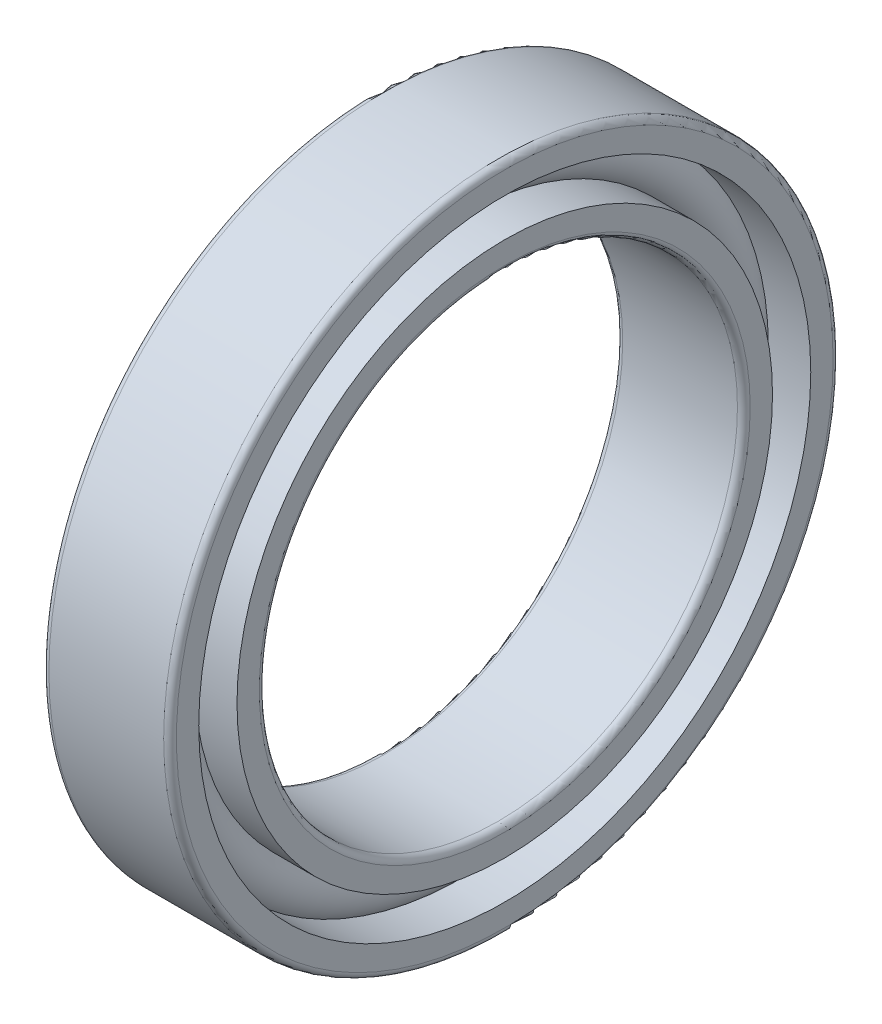
SolidWorks part; units mm, degrees
ref_plane "Plane1" through (0, 0, 0) normal (0, 0, 1) x (1, 0, 0)
ref_plane "Plane2" through (0, 0, 0) normal (0, 1, 0) x (1, 0, 0)
ref_plane "Plane3" through (0, 0, 0) normal (1, 0, 0) x (0, 0, -1)
other "Configuration Table"
sketch "Clipboard" plane through (0, 0, 0) normal (0, 0, 1) x (1, 0, 0)
  line L0 (-10, 0) -> (10, 0) construction
  line L1 (0, 0) -> (22.3471, -0.7804)
  line L2 (0, 0) -> (8.9945, 0.3141)
  line L3 (0, 0) -> (22.3471, -0.7804)
  line L4 (0, 0) -> (-22.3573, -0.3902)
  dimension "BallCLRad" = 9
sketch "CagSpiSke" plane through (0, 0, 0) normal (0, 0, 1) x (1, 0, 0)
  line L0 (0.09, 8.85) -> (0.09, 9.15)
  line L1 (0.09, 9.15) -> (-0.09, 9.15)
  line L2 (-0.09, 9.15) -> (-0.09, 8.85)
  line L3 (-0.09, 8.85) -> (0.09, 8.85)
  line L4 (-20.6375, 0) -> (20.6375, 0) construction
  line L5 (0, 0) -> (0, 23.7692) construction
  dimension "OD" = 18.3
  dimension "ID" = 17.7
revolve "CageSpine" add sketch "CagSpiSke" angle 0.001 about L4 reverse direction yes
ref_axis "Axis1" through (-50, 0, 0) along (1, 0, 0)
sketch "CagBalSke" plane through (0, 0, 0) normal (0, 0, 1) x (1, 0, 0)
  line L0 (-0.99, 9) -> (0.99, 9)
  line L1 (-1.905, 9) -> (1.905, 9) construction
  line L2 (-10, 0) -> (10, 0) construction
  line L3 (0, 0) -> (0, 24) construction
  arc A0 (0.99, 9) -> (-0.99, 9) centre (0, 9) cw
  dimension "BallCLRad" = 9
revolve "CageBall" [suppressed] add sketch "CagBalSke" angle 360 about L1 reverse direction yes
pattern_circular "CageBalls" [suppressed] count 2 every 180 about axis through (-50, 0, 0) along (1, 0, 0)
sketch "CagTrmODSke" plane through (0, 0, 0) normal (0, 0, 1) x (1, 0, 0)
  line L0 (0.991, 9.15) -> (0.991, 9.991)
  line L1 (0.991, 9.991) -> (-0.991, 9.991)
  line L2 (-0.991, 9.991) -> (-0.991, 9.15)
  line L3 (-0.991, 9.15) -> (0.991, 9.15)
  line L4 (-20.6375, 0) -> (20.6375, 0) construction
  line L5 (0, 0) -> (0, 25) construction
  dimension "Width" = 1.982
  dimension "ID" = 18.3
  dimension "OD" = 19.982
revolve "CageTrimOD" [suppressed] cut sketch "CagTrmODSke" angle 360 about L4 reverse direction yes
sketch "CagTrmIDSke" plane through (0, 0, 0) normal (0, 0, 1) x (1, 0, 0)
  line L0 (0.991, 8.011) -> (0.991, 8.85)
  line L1 (0.991, 8.85) -> (-0.991, 8.85)
  line L2 (-0.991, 8.85) -> (-0.991, 8.011)
  line L3 (-0.991, 8.011) -> (0.991, 8.011)
  line L4 (-20.6375, 0) -> (20.6375, 0) construction
  line L5 (0, 0) -> (0, 25) construction
  dimension "Width" = 1.982
  dimension "ID" = 16.022
  dimension "OD" = 17.7
revolve "CageTrimID" [suppressed] cut sketch "CagTrmIDSke" angle 360 about L4 reverse direction yes
sketch "BalSimSke" plane through (0, 0, 0) normal (0, 0, 1) x (1, 0, 0)
  line L0 (-10, 0) -> (10, 0) construction
  line L1 (-10, 9) -> (10, 9) construction
  line L2 (0, 0) -> (0, 23) construction
  circle A0 centre (0, 9) radius 0.9
  dimension "BallCLRad" = 9
  dimension "Ball_diameter" = 1.8
revolve "BallsSimplified" add sketch "BalSimSke" angle 360 about L0
sketch "BalDetSke" plane through (0, 0, 0) normal (0, 0, 1) x (1, 0, 0)
  line L0 (-0.9, 9) -> (0.9, 9)
  line L1 (-1.905, 9) -> (1.905, 9) construction
  line L2 (0, 0) -> (0, 25) construction
  arc A0 (0.9, 9) -> (-0.9, 9) centre (0, 9) cw
  dimension "BallCLRad" = 9
  dimension "Ball_diameter" = 1.8
revolve "BallDetailed" [suppressed] add sketch "BalDetSke" angle 360 about L1 reverse direction yes
sketch "InnRacSke" plane through (0, 0, 0) normal (0, 0, 1) x (1, 0, 0)
  line L0 (-0.6369, 8.4) -> (-2, 8.4)
  line L1 (-2, 8.4) -> (-2, 7.7)
  line L2 (-1.8, 7.5) -> (1.8, 7.5)
  line L3 (2, 7.7) -> (2, 8.4)
  line L4 (2, 8.4) -> (0.6369, 8.4)
  line L5 (-20.6375, 0) -> (20.6375, 0) construction
  line L6 (0, 0) -> (0, 30) construction
  arc A0 (-2, 7.7) -> (-1.8, 7.5) centre (-1.8, 7.7) ccw
  arc A1 (1.8, 7.5) -> (2, 7.7) centre (1.8, 7.7) ccw
  arc A2 (0.6369, 8.4) -> (-0.6369, 8.4) centre (0, 9) cw
  dimension "BallCLRad" = 9
  dimension "Fillet_radius" = 0.2
  dimension "Ball_diameter" = 1.75
  dimension "ID" = 15
  dimension "OD" = 16.8
  dimension "Width" = 4
revolve "InnerRace" add sketch "InnRacSke" angle 360 about L5 reverse direction yes
sketch "OutRacSke" plane through (0, 0, 0) normal (0, 0, 1) x (1, 0, 0)
  line L0 (-0.6369, 9.6) -> (-2, 9.6)
  line L1 (-2, 9.6) -> (-2, 10.3)
  line L2 (-1.8, 10.5) -> (1.8, 10.5)
  line L3 (2, 10.3) -> (2, 9.6)
  line L4 (2, 9.6) -> (0.6369, 9.6)
  line L5 (-20.6375, 0) -> (20.6375, 0) construction
  line L6 (0, 0) -> (0, 30) construction
  arc A0 (-2, 10.3) -> (-1.8, 10.5) centre (-1.8, 10.3) cw
  arc A1 (1.8, 10.5) -> (2, 10.3) centre (1.8, 10.3) cw
  arc A2 (0.6369, 9.6) -> (-0.6369, 9.6) centre (0, 9) ccw
  dimension "BallCLRad" = 9
  dimension "Fillet_radius" = 0.2
  dimension "Ball_diameter" = 1.75
  dimension "Width" = 4
revolve "OuterRace" add sketch "OutRacSke" angle 360 about L5 reverse direction yes
pattern_circular "BallsDetailed" [suppressed] count 2 every 180 about axis through (-50, 0, 0) along (1, 0, 0)
equation "\"BallCLRad@Clipboard\" = ( \"OD@OutRacSke\" + \"ID@InnRacSke\" ) / 4"
equation "\"BallCLRad@BalSimSke\" = \"BallCLRad@Clipboard\""
equation "\"BallCLRad@BalDetSke\" = \"BallCLRad@Clipboard\""
equation "\"BallCLRad@InnRacSke\" = \"BallCLRad@Clipboard\""
equation "\"BallCLRad@OutRacSke\" = \"BallCLRad@Clipboard\""
equation "\"Ball_diameter@InnRacSke\" = \"Ball_diameter@BalDetSke\" - 0.05"
equation "\"Ball_diameter@OutRacSke\" = \"Ball_diameter@BalDetSke\" - 0.05"
equation "\"Ball_diameter@BalSimSke\" = \"Ball_diameter@BalDetSke\""
equation "\"Fillet_radius@OutRacSke\" = \"Fillet_radius@InnRacSke\""
equation "\"Max_count@Clipboard\" = int( 3.14159265 / atn(( \"Ball_diameter@BalDetSke\" / 2) / sqr( \"BallCLRad@Clipboard\"  *  \"BallCLRad@Clipboard\" - ( \"Ball_diameter@BalDetSke\" / 2) *  ( \"Ball_diameter@BalDetSke\" / 2))))"
equation "\"Max_count@Clipboard\" = ((sgn( \"Max_count@Clipboard\" - \"Count@Clipboard\" )-1)*( \"Max_count@Clipboard\" - \"Count@Clipboard\" ))/-2+ \"Count@Clipboard\""
equation "\"Count@BallsDetailed\" = int( \"Show_count@Clipboard\" ) "
equation "\"Count@BallsDetailed\" = ((sgn( \"Count@BallsDetailed\" - \"Max_count@Clipboard\" )-1)*( \"Count@BallsDetailed\" - \"Max_count@Clipboard\" ))/-2+ \"Max_count@Clipboard\""
equation "\"Count@BallsDetailed\" = ((sgn( \"Count@BallsDetailed\" - \"Min_count@Clipboard\" )+1)*( \"Count@BallsDetailed\" - \"Min_count@Clipboard\"))/2 +\"Min_count@Clipboard\""
equation "\"Angle@BallsDetailed\" = 360.0 / \"Max_count@Clipboard\""
equation "\"BallCLRad@CagBalSke\" = \"BallCLRad@Clipboard\""
equation "\"Count@CageBalls\" = \"Count@BallsDetailed\""
equation "\"Angle@CageBalls\" = \"Angle@BallsDetailed\""
equation "\"Angle@CageSpine\" =  \"Angle@CageBalls\" * ( \"Count@CageBalls\" -1 + int( \"Count@CageBalls\" / \"Max_count@Clipboard\" ) )  + 0.001 -  int( \"Count@CageBalls\" / \"Max_count@Clipboard\" ) * 0.001"
equation "\"Angle@CageSpine\" =  \"Angle@CageSpine\" * int( \"Min_count@Clipboard\" / 2) + int(1 / \"Min_count@Clipboard\")  * 0.001"
equation "\"CageWallOD@CagBalSke\" =  \"Ball_diameter@BalDetSke\" * 1.1"
equation "\"Thickness@CagSpiSke\" =  \"Ball_diameter@BalDetSke\" * 0.1"
equation "\"OD@CagTrmODSke\" = \"BallCLRad@Clipboard\" * 2 + \"CageWallOD@CagBalSke\" + 0.002"
equation "\"ID@CagTrmODSke\" = \"BallCLRad@Clipboard\" * 2 + \"Ball_diameter@BalDetSke\" / 6"
equation "\"OD@CagTrmIDSke\" = \"BallCLRad@Clipboard\" * 2 - \"Ball_diameter@BalDetSke\" / 6"
equation "\"ID@CagTrmIDSke\" = \"BallCLRad@Clipboard\" * 2 - \"CageWallOD@CagBalSke\" + 0.002"
equation "\"OD@CagSpiSke\" = \"ID@CagTrmODSke\""
equation "\"ID@CagSpiSke\" = \"OD@CagTrmIDSke\""
equation "\"Width@CagTrmODSke\" = \"CageWallOD@CagBalSke\" + 0.002"
equation "\"Width@CagTrmIDSke\" = \"CageWallOD@CagBalSke\" + 0.002"
